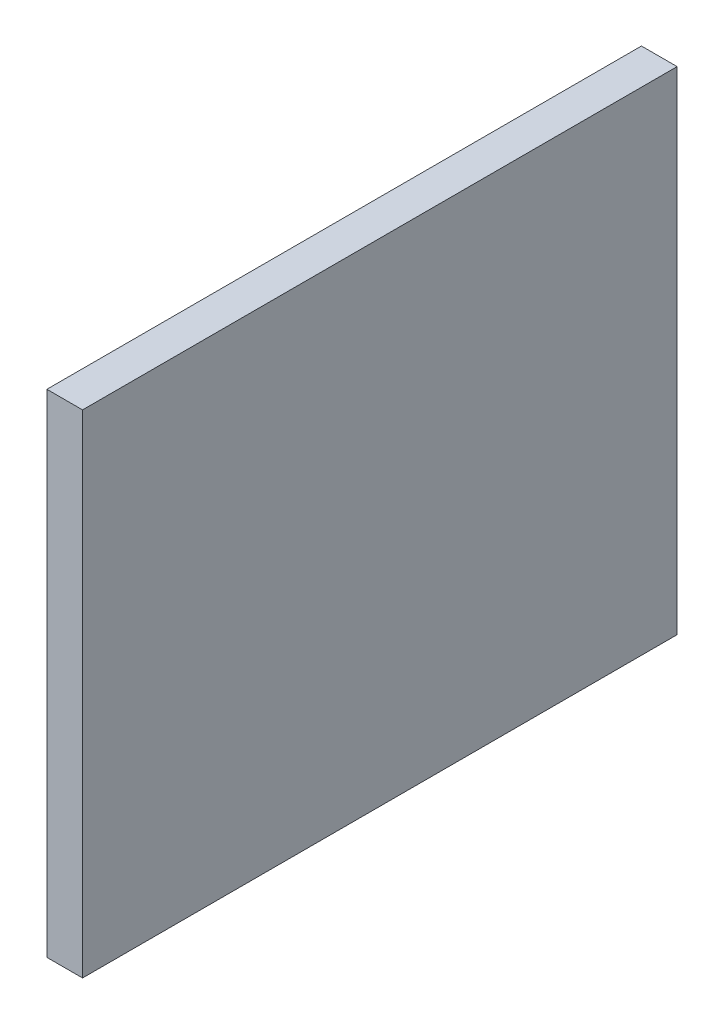
SolidWorks part; units mm, degrees
ref_plane "Front Plane" through (0, 0, 0) normal (0, 0, 1) x (1, 0, 0)
ref_plane "Top Plane" through (0, 0, 0) normal (0, 1, 0) x (1, 0, 0)
ref_plane "Right Plane" through (0, 0, 0) normal (1, 0, 0) x (0, 0, -1)
sketch "Sketch1" plane through (0, 0, 0) normal (0, 0, 1) x (1, 0, 0)
  line L0 (-119, 208) -> (-131, 208)
  line L1 (-119, 165) -> (-119, 208)
  line L2 (-12, 208) -> (-148, 208) construction
  line L3 (-119, 165) -> (-119, 42.5)
  line L4 (-148, 42.5) -> (-12, 42.5) construction
  line L5 (-119, 42.5) -> (-131, 42.5)
  line L6 (-131, 42.5) -> (-131, 208)
extrude "Boss-Extrude1" add sketch "Sketch1" along normal up to surface (200 mm away)
